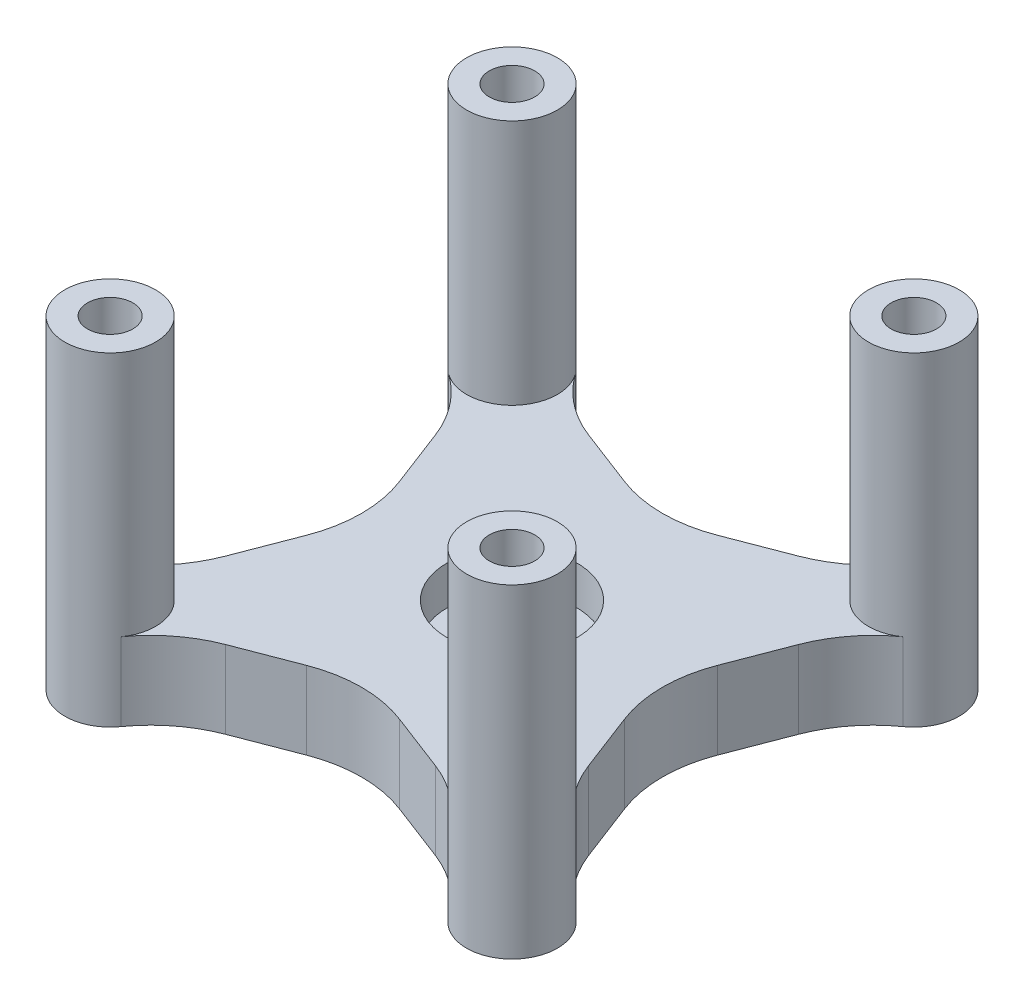
SolidWorks part; units mm, degrees
ref_plane "Piano frontale" through (0, 0, 0) normal (0, 0, 1) x (1, 0, 0)
ref_plane "Piano superiore" through (0, 0, 0) normal (0, 1, 0) x (1, 0, 0)
ref_plane "Piano destro" through (0, 0, 0) normal (1, 0, 0) x (0, 0, -1)
sketch "Schizzo1" plane through (0, 0, 0) normal (0, 1, 0) x (1, 0, 0)
  line L0 (-15.5, -12) -> (-10.9, 0)
  line L1 (15.5, -15.5) -> (-15.5, -15.5) construction
  line L2 (15.5, -15.5) -> (15.5, 15.5) construction
  line L3 (15.5, 15.5) -> (-15.5, 15.5) construction
  line L4 (-15.5, -15.5) -> (-15.5, 15.5) construction
  line L5 (15.5, -15.5) -> (-15.5, 15.5) construction
  line L6 (15.5, 15.5) -> (-15.5, -15.5) construction
  line L7 (-10.9, 0) -> (-15.5, 12)
  line L8 (-12, 15.5) -> (0, 10.9)
  line L9 (0, 10.9) -> (12, 15.5)
  line L10 (15.5, 12) -> (10.9, 0)
  line L11 (10.9, 0) -> (15.5, -12)
  line L12 (-12, -15.5) -> (0, -10.9)
  line L13 (0, -10.9) -> (12, -15.5)
  circle A0 centre (0, 0) radius 10.9
  circle A1 centre (-15.5, 15.5) radius 1.75
  circle A2 centre (15.5, 15.5) radius 1.75
  circle A3 centre (15.5, -15.5) radius 1.75
  circle A4 centre (-15.5, -15.5) radius 1.75
  circle A5 centre (0, 0) radius 3
  circle A6 centre (0, 0) radius 5
  circle A7 centre (-15.5, 15.5) radius 3.5
  circle A8 centre (15.5, 15.5) radius 3.5
  circle A9 centre (15.5, -15.5) radius 3.5
  circle A10 centre (-15.5, -15.5) radius 3.5
  point P0 (0, 0)
  dimension "D3" = 21.8
  dimension "D4" = 10
  dimension "D5" = 6
  dimension "D6" = 3.5
  dimension "D7" = 3.5
  dimension "D8" = 3.5
  dimension "D9" = 3.5
  dimension "D10" = 7
  dimension "D11" = 7
  dimension "D12" = 7
  dimension "D13" = 7
  dimension "D1" = 31
  dimension "D2" = 31
extrude "Estrusione-Estrusione1" add sketch "Schizzo1" along normal blind 25 contours A10 A4 | A7 A1 | A8 A2 | A9 A3 region at (-13.0951, 0, 13.0951) region at (-17.9049, 0, -17.9049) region at (15.5, 0, -18.901) region at (13.0951, 0, 13.0951)
extrude "Estrusione-Estrusione2" add sketch "Schizzo1<3>" along normal blind 3 contours A10 L12 A0 L0 | A9 L11 A0 L13 | A8 L9 A0 L10 | A7 L7 A0 L8 | A0 A6 | A6 A5 region at (-9.7368, 0, 9.7368) region at (-9.7368, 0, -9.7368) region at (-7.4895, 0, -7.4895) region at (9.7368, 0, -9.7368) region at (9.7368, 0, 9.7368) region at (-4.8586, 0, 0)
sketch "Schizzo1<3>" plane through (0, 0, 0) normal (0, 1, 0) x (1, 0, 0) same geometry as "Schizzo1"
extrude "Estrusione-Estrusione4" add sketch "Schizzo1<5>" along normal blind 3 from surface contours A0 A6 | A10 L12 A0 L0 | A7 L7 A0 L8 | A8 L9 A0 L10 | A9 L11 A0 L13 region at (-9.7368, 0, 9.7368) region at (-9.7368, 0, -9.7368) region at (-7.4895, 0, -7.4895) region at (9.7368, 0, -9.7368) region at (9.7368, 0, 9.7368) starting at face at (0, 3, 0)
sketch "Schizzo1<5>" plane through (0, 0, 0) normal (0, 1, 0) x (1, 0, 0) same geometry as "Schizzo1"
fillet "Raccordo1" radius 10 12 edges at (-15.5, 3, 12) (-10.9, 3, 0) (-15.5, 3, -12) (-12, 3, -15.5) (0, 3, -10.9) (12, 3, -15.5) (15.5, 3, -12) (10.9, 3, 0) (15.5, 3, 12) (12, 3, 15.5) (0, 3, 10.9) (-12, 3, 15.5)
equation "\"D7@Schizzo1\"=\"D6@Schizzo1\""
equation "\"D8@Schizzo1\"=\"D6@Schizzo1\""
equation "\"D9@Schizzo1\"=\"D6@Schizzo1\""
equation "\"D11@Schizzo1\"=\"D10@Schizzo1\""
equation "\"D12@Schizzo1\"=\"D10@Schizzo1\""
equation "\"D13@Schizzo1\"=\"D10@Schizzo1\""
